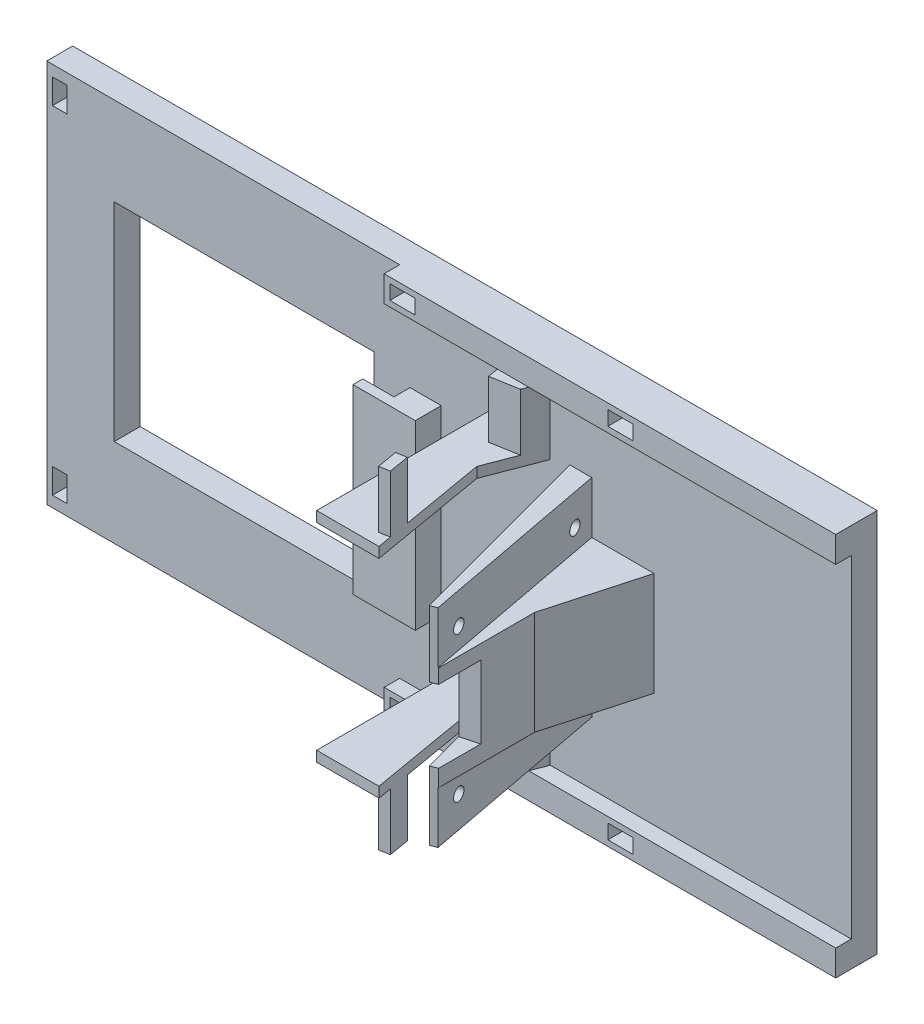
SolidWorks part; units mm, degrees
other "Marca1"
sketch "Croquis45" plane through (-59, -35, 38.8) normal (-0.8813, -0.0586, 0.4689) x (0.3892, -0.6526, 0.6501)
sketch "Croquis46" plane through (-59, -35, 38.8) normal (-0.8813, -0.0586, 0.4689) x (0.3892, -0.6526, 0.6501)
ref_plane "Alzado" through (0, 0, 0) normal (0, 0, 1) x (1, 0, 0)
ref_plane "Planta" through (0, 0, 0) normal (0, 1, 0) x (1, 0, 0)
ref_plane "Vista lateral" through (0, 0, 0) normal (1, 0, 0) x (0, 0, -1)
sketch "Croquis1" plane through (0, 0, 0) normal (0, 0, 1) x (1, 0, 0)
  line L1 (-59, -37) -> (59, -37)
  line L2 (-59, -37) -> (-59, 37)
  line L3 (-59, 37) -> (59, 37)
  line L4 (59, -37) -> (59, 37)
  line L5 (-59, -37) -> (59, 37) construction
  line L6 (-59, 37) -> (59, -37) construction
  point P0 (0, 0)
extrude "Saliente-Extruir1" add sketch "Croquis1" along normal blind 5
sketch "Croquis2" plane through (0, 0, 5) normal (0, 0, 1) x (1, 0, 0)
  line L4 (-46, 20) -> (4, 20)
  line L5 (4, 20) -> (4, -20)
  line L6 (4, -20) -> (-46, -20)
  line L7 (-46, -20) -> (-46, 20)
extrude "Cortar-Extruir1" cut sketch "Croquis2" against normal blind 5
sketch "Croquis3" plane through (0, 0, 5) normal (0, 0, 1) x (1, 0, 0)
  line L0 (59, 37) -> (59, 32)
  line L1 (59, -37) -> (59, 37) construction
  line L2 (59, 32) -> (9, 32)
  line L3 (9, 32) -> (9, 37)
  line L4 (59, 37) -> (-59, 37) construction
  line L5 (9, 37) -> (59, 37)
  line L6 (59, -37) -> (59, -32)
  line L7 (59, -32) -> (9, -32)
  line L8 (9, -32) -> (9, -37)
  line L9 (-59, -37) -> (59, -37) construction
  line L10 (9, -37) -> (59, -37)
extrude "Saliente-Extruir2" add sketch "Croquis3" along normal blind 3
sketch "Croquis4" plane through (0, 0, 8) normal (0, 0, 1) x (1, 0, 0)
  line L0 (59, 37) -> (9, 37) construction
  line L5 (56.9, 35.9) -> (52.1, 35.9)
  line L6 (56.9, 35.9) -> (56.9, 33.1)
  line L7 (56.9, 33.1) -> (52.1, 33.1)
  line L8 (52.1, 35.9) -> (52.1, 33.1)
  line L9 (10.1, 35.9) -> (14.9, 35.9)
  line L10 (10.1, 35.9) -> (10.1, 33.1)
  line L11 (10.1, 33.1) -> (14.9, 33.1)
  line L12 (14.9, 35.9) -> (14.9, 33.1)
  line L13 (10.1, -33.1) -> (14.9, -33.1)
  line L14 (10.1, -33.1) -> (10.1, -35.9)
  line L15 (10.1, -35.9) -> (14.9, -35.9)
  line L16 (14.9, -33.1) -> (14.9, -35.9)
  line L17 (56.9, -33.1) -> (52.1, -33.1)
  line L18 (56.9, -33.1) -> (56.9, -35.9)
  line L19 (56.9, -35.9) -> (52.1, -35.9)
  line L20 (52.1, -33.1) -> (52.1, -35.9)
  line L21 (-57.9, -34.9) -> (-55.1, -34.9)
  line L22 (-57.9, -34.9) -> (-57.9, -30.1)
  line L23 (-57.9, -30.1) -> (-55.1, -30.1)
  line L24 (-55.1, -34.9) -> (-55.1, -30.1)
  line L25 (-57.9, 34.9) -> (-55.1, 34.9)
  line L26 (-57.9, 34.9) -> (-57.9, 30.1)
  line L27 (-57.9, 30.1) -> (-55.1, 30.1)
  line L28 (-55.1, 34.9) -> (-55.1, 30.1)
  line L29 (9, 37) -> (9, 32) construction
  line L30 (9, -37) -> (59, -37) construction
  line L31 (-59, 37) -> (-59, -37) construction
  line L32 (9, 37) -> (-59, 37) construction
  line L33 (-59, -37) -> (9, -37) construction
  line L34 (59, -37) -> (59, -32) construction
  line L35 (59, 32) -> (59, 37) construction
  dimension "D1" = 1.1
  dimension "D2" = 1.1
  dimension "D3" = 1.1
  dimension "D4" = 1.1
  dimension "D5" = 1.1
  dimension "D6" = 2.1
  dimension "D7" = 1.1
  dimension "D8" = 2.1
  dimension "D9" = 1.1
  dimension "D10" = 2.1
  dimension "D11" = 2.1
extrude "Cortar-Extruir2" cut sketch "Croquis4" against normal blind 6
sketch "Croquis5" plane through (0, 0, 5) normal (0, 0, 1) x (1, 0, 0)
  line L0 (41, -20) -> (41, 20)
  line L1 (41, 20) -> (38, 20)
  line L2 (38, 20) -> (38, -20)
  line L3 (38, -20) -> (41, -20)
  line L4 (38, 0) -> (4, 0) construction
  line L5 (4, -20) -> (4, 20) construction
  point P0 (41, -20)
extrude "Cortar-Extruir3" cut sketch "Croquis5" against normal blind 3
sketch "Croquis6" plane through (0, 0, 2) normal (0, 0, 1) x (1, 0, 0)
  line L0 (41, 20) -> (41, -20)
  line L1 (41, -20) -> (53, -20)
  line L2 (38, -20) -> (41, -20) construction
  line L3 (53, -20) -> (53, 20)
  line L4 (41, 20) -> (38, 20) construction
  line L5 (53, 20) -> (41, 20)
extrude "Saliente-Extruir3" add sketch "Croquis6" along normal blind 40
sketch "Croquis7" plane through (0, -20, 0) normal (0, -1, 0) x (1, 0, 0)
  line L0 (41, 42) -> (51.718, 42) construction
  line L1 (53, 42) -> (41, 42) construction
  line L2 (51.718, 42) -> (41, 2)
  line L3 (41, 2) -> (41, 42)
  line L4 (41, 42) -> (51.718, 42)
  line L5 (38, 2) -> (41, 2) construction
  line L6 (41, 2) -> (41, 5) construction
  line L7 (53, 42) -> (41, 42) construction
  dimension "D1" = 15
sketch "Croquis8" plane through (0, 0, 5) normal (0, 0, 1) x (1, 0, 0)
  line L1 (17, 17.5) -> (17, -17.5)
  line L2 (17, -17.5) -> (13, -17.5)
  line L3 (13, -17.5) -> (13, 17.5)
  line L4 (13, 17.5) -> (17, 17.5)
extrude "Saliente-Extruir5" add sketch "Croquis8" along normal blind 5
sketch "Croquis10" plane through (13, 0, 0) normal (-1, 0, 0) x (0, 0, 1)
  line L0 (10, 17.5) -> (10, -17.5)
  line L6 (10, 17.5) -> (8.1, 17.5)
  line L7 (8.1, 17.5) -> (8.1, -17.5)
  line L8 (8.1, -17.5) -> (10, -17.5)
sketch "Croquis12" plane through (0, 0, 5) normal (0, 0, 1) x (1, 0, 0)
  line L0 (26, -19) -> (38, -19)
  line L2 (38, -19) -> (38, -32)
  line L3 (38, -32) -> (31, -32)
  line L5 (31, 32) -> (38, 32)
  line L8 (38, 32) -> (38, 19)
  line L9 (26, -19) -> (26, -21)
  line L10 (26, -21) -> (31, -21)
  line L11 (26, 19) -> (38, 19)
  line L12 (26, 19) -> (26, 21)
  line L13 (26, 21) -> (31, 21)
  line L14 (31, 32) -> (31, 21)
  line L15 (31, -21) -> (31, -32)
extrude "Saliente-Extruir7" add sketch "Croquis12" along normal blind 33
sketch "Croquis14" plane through (0, 32, 0) normal (0, 1, 0) x (1, 0, 0)
  line L0 (31, -38) -> (36, -38)
  line L1 (31, -38) -> (38, -38) construction
  line L2 (36, -38) -> (31, -9)
  line L3 (31, -38) -> (31, -5) construction
  line L4 (31, -9) -> (31, -38)
extrude "Cortar-Extruir6" cut sketch "Croquis14" against normal blind 11
sketch "Croquis16" plane through (0, 19, 0) normal (0, -1, 0) x (1, 0, 0)
  line L0 (38, 38) -> (38, 5)
  line L1 (38, 5) -> (33, 5)
  line L2 (33, 5) -> (33, 9)
  line L4 (38, 38) -> (33, 9)
extrude "Cortar-Extruir7" cut sketch "Croquis16" against normal blind 13
sketch "Croquis17" plane through (0, -32, 0) normal (0, -1, 0) x (1, 0, 0)
  line L0 (38, 38) -> (38, 5)
  line L1 (38, 5) -> (33, 5)
  line L2 (33, 5) -> (33, 9)
  line L3 (38, 38) -> (33, 9)
extrude "Cortar-Extruir8" cut sketch "Croquis17" against normal blind 13
sketch "Croquis18" plane through (0, -32, 0) normal (0, -1, 0) x (1, 0, 0)
  line L0 (31, 38) -> (36, 38)
  line L1 (36, 38) -> (31, 9)
  line L2 (31, 38) -> (31, 8) construction
  line L3 (31, 9) -> (31, 38)
extrude "Cortar-Extruir9" cut sketch "Croquis18" against normal blind 11
extrude "Saliente-Extruir9" add sketch "Croquis10" along normal blind 8
sketch "Croquis22" plane through (13, 0, 0) normal (-1, 0, 0) x (0, 0, 1)
  line L0 (8.1, -17.5) -> (5, -17.5)
  line L1 (5, -17.5) -> (5, 17.5)
  line L2 (5, 17.5) -> (8.1, 17.5)
  line L3 (8.1, 17.5) -> (5, 17.5) construction
  line L4 (8.1, 17.5) -> (8.1, -17.5)
extrude "Saliente-Extruir10" add sketch "Croquis22" along normal blind 2
extrude "Cortar-Extruir11" cut sketch "Croquis7" against normal blind 40
sketch "Croquis23" plane through (38, 0, 0) normal (1, 0, 0) x (0, 0, -1)
  line L0 (-2, 20) -> (-5, 20)
  line L1 (-5, 20) -> (-5, -20)
  line L2 (-5, -20) -> (-2, -20)
  line L3 (-2, -20) -> (-2, 20)
extrude "Saliente-Extruir11" add sketch "Croquis23" along normal blind 10
sketch "Croquis25" plane through (0, -20, 0) normal (0, -1, 0) x (1, 0, 0)
  line L0 (53, 42) -> (53, 5)
  line L1 (53, 5) -> (46, 5)
  line L3 (46, 5) -> (53, 42)
  line L4 (51.718, 42) -> (53, 42) construction
  line L7 (51.718, 42) -> (53, 42) construction
extrude "Cortar-Extruir12" cut sketch "Croquis25" against normal blind 10
sketch "Croquis26" plane through (0, 20, 0) normal (0, 1, 0) x (1, 0, 0)
  line L0 (53, -5) -> (53, -42)
  line L1 (53, -42) -> (46, -5)
  line L3 (46, -5) -> (53, -5)
  line L4 (51.718, -42) -> (53, -42) construction
extrude "Cortar-Extruir13" cut sketch "Croquis26" against normal blind 10
sketch "Croquis27" plane through (0, -20, 0) normal (0, -1, 0) x (1, 0, 0)
  line L0 (51.718, 42) -> (53, 42)
  line L1 (53, 42) -> (53, 41.4949)
  line L3 (53, 41.4949) -> (51.718, 42)
  line L4 (53, 5) -> (53, 42) construction
extrude "Cortar-Extruir14" cut sketch "Croquis27" against normal blind 40
sketch "Croquis28" plane through (37.7535, 0, -10.116) normal (-0.9659, 0, 0.2588) x (0.2588, 0, 0.9659)
  line L0 (20.8019, -14) -> (48.8019, -14) construction
  line L1 (48.8019, -14) -> (48.8019, 14) construction
  line L2 (48.8019, 14) -> (20.8019, 14) construction
  line L3 (20.8019, 14) -> (20.8019, -14) construction
  line L4 (20.8019, 14) -> (48.8019, -14) construction
  line L5 (48.8019, 14) -> (20.8019, -14) construction
  line L6 (34.8019, 0) -> (44.3019, 0) construction
  line L7 (44.3019, 0) -> (44.3019, 12.5) construction
  line L8 (44.3019, 12.5) -> (26.3019, 12.5) construction
  line L9 (26.3019, 12.5) -> (26.3019, -12.5) construction
  line L10 (26.3019, -12.5) -> (44.3019, -12.5) construction
  line L11 (44.3019, -12.5) -> (44.3019, 0) construction
  line L12 (34.8019, 20) -> (34.8019, -20) construction
  line L14 (15.6493, 20) -> (53.9545, 20) construction
  line L15 (15.6493, -20) -> (53.9545, -20) construction
  line L16 (53.9545, 0) -> (15.6493, 0) construction
  line L17 (53.9545, 20) -> (53.9545, -20) construction
  line L18 (15.6493, -20) -> (15.6493, 20) construction
  circle A0 centre (20.8019, 14) radius 1.25
  circle A1 centre (48.8019, 14) radius 1.25
  circle A2 centre (48.8019, -14) radius 1.25
  circle A3 centre (20.8019, -14) radius 1.25
  point P8 (34.8019, 0)
  point P28 (34.8019, 0)
extrude "Cortar-Extruir15" cut sketch "Croquis28" against normal blind 5
sketch "Croquis29" plane through (59, 0, 0) normal (1, 0, 0) x (0, 0, -1)
  line L2 (-8, 37) -> (0, 37)
  line L3 (0, 37) -> (0, -37)
  line L4 (0, -37) -> (-8, -37)
  line L5 (-8, -37) -> (-8, -32)
  line L6 (-8, -32) -> (-5, -32)
  line L7 (-5, -32) -> (-5, 32)
  line L8 (-8, 37) -> (-8, 32)
  line L9 (-8, 32) -> (-5, 32)
extrude "Saliente-Extruir12" add sketch "Croquis29" along normal blind 37
ref_plane "Plano1" through (28.5982, 0, -4.9307) normal (-0.9855, 0, 0.1699) x (0.1699, 0, 0.9855)
sketch "Croquis30" plane through (28.5982, 0, -4.9307) normal (-0.9855, 0, 0.1699) x (0.1699, 0, 0.9855)
  line L1 (14.1363, 32) -> (43.5641, 32)
  line L2 (14.1363, 32) -> (14.1363, 21)
  line L3 (14.1363, 21) -> (43.5641, 21)
  line L4 (43.5641, 32) -> (43.5641, 21)
extrude "Saliente-Extruir13" add sketch "Croquis30" against normal up to surface (1.9709 mm away) up to face at (35.5, 25.5, 23.5)
sketch "Croquis31" plane through (28.5982, 0, -4.9307) normal (-0.9855, 0, 0.1699) x (0.1699, 0, 0.9855)
  line L0 (23.1363, 26.5) -> (32.1363, 26.5) construction
  line L1 (14.1363, 21) -> (14.1363, 32) construction
  line L3 (14.1363, 26.5) -> (23.1363, 26.5) construction
  line L4 (32.1363, 26.5) -> (41.1363, 26.5) construction
  line L5 (14.1363, 31) -> (14.1363, 22) construction
  line L6 (14.1363, 31) -> (43.5641, 31) construction
  line L7 (43.5641, 21) -> (43.5641, 32) construction
  line L8 (14.1363, 22) -> (43.5641, 22) construction
  line L9 (23.1363, 31) -> (23.1363, 22) construction
  line L10 (14.1363, 31) -> (16.1363, 31)
  line L11 (14.1363, 31) -> (14.1363, 22)
  line L12 (14.1363, 22) -> (16.1363, 22)
  line L13 (16.1363, 31) -> (16.1363, 22)
  line L14 (32.1363, 31) -> (32.1363, 22) construction
  line L16 (23.1363, 31) -> (25.1363, 31)
  line L17 (23.1363, 31) -> (23.1363, 22)
  line L18 (23.1363, 22) -> (25.1363, 22)
  line L19 (25.1363, 31) -> (25.1363, 22)
  line L20 (32.1363, 31) -> (34.1363, 31)
  line L21 (32.1363, 31) -> (32.1363, 22)
  line L22 (32.1363, 22) -> (34.1363, 22)
  line L23 (34.1363, 31) -> (34.1363, 22)
  point P10 (14.1363, 26.5)
  point P18 (23.1363, 26.5)
  point P21 (32.1363, 26.5)
  dimension "D1" = 9
  dimension "D2" = 9
  dimension "D3" = 9
  dimension "D4" = 9
  dimension "D5" = 2
  dimension "D6" = 2
  dimension "D7" = 2
extrude "Saliente-Extruir14" [suppressed] add sketch "Croquis31" along normal blind 3
sketch "Croquis34" [suppressed] plane through (3.0034, 0, 16.2186) normal (0.1821, 0, 0.9833) x (0.9833, 0, -0.1821)
  line L0 (28.8429, 25.5) -> (25.8429, 25.5) construction
  line L1 (28.8429, 21) -> (28.8429, 30) construction
  line L2 (25.8429, 21) -> (25.8429, 30) construction
  line L3 (25.8429, 29) -> (25.8429, 22) construction
  line L5 (25.8429, 29) -> (28.8429, 29)
  line L6 (25.8429, 29) -> (25.8429, 22)
  line L7 (25.8429, 22) -> (28.8429, 22)
  line L8 (28.8429, 29) -> (28.8429, 22)
  point P9 (25.8429, 25.5)
  dimension "D1" = 7
extrude "Cortar-Extruir16" [suppressed] cut sketch "Croquis34" against normal blind 1
sketch "Croquis35" [suppressed] plane through (4.6422, 0, 25.0681) normal (0.1821, 0, 0.9833) x (0.9833, 0, -0.1821)
  line L0 (28.8429, 25.5) -> (25.8429, 25.5) construction
  line L1 (28.8429, 21) -> (28.8429, 30) construction
  line L2 (25.8429, 21) -> (25.8429, 30) construction
  line L3 (25.8429, 29) -> (25.8429, 22) construction
  line L5 (25.8429, 29) -> (28.8429, 29)
  line L6 (25.8429, 29) -> (25.8429, 22)
  line L7 (25.8429, 22) -> (28.8429, 22)
  line L8 (28.8429, 29) -> (28.8429, 22)
  point P9 (25.8429, 25.5)
  dimension "D1" = 7
extrude "Cortar-Extruir17" [suppressed] cut sketch "Croquis35" against normal blind 1
sketch "Croquis36" [suppressed] plane through (6.281, 0, 33.9176) normal (0.1821, 0, 0.9833) x (0.9833, 0, -0.1821)
  line L0 (28.8429, 25.5) -> (25.8429, 25.5) construction
  line L1 (28.8429, 21) -> (28.8429, 30) construction
  line L2 (25.8429, 21) -> (25.8429, 30) construction
  line L3 (25.8429, 29) -> (25.8429, 22) construction
  line L5 (25.8429, 29) -> (28.8429, 29)
  line L6 (25.8429, 29) -> (25.8429, 22)
  line L7 (25.8429, 22) -> (28.8429, 22)
  line L8 (28.8429, 29) -> (28.8429, 22)
  point P9 (25.8429, 25.5)
  dimension "D1" = 7
extrude "Cortar-Extruir18" [suppressed] cut sketch "Croquis36" against normal blind 1
sketch "Croquis37" [suppressed] plane through (28.3607, 0, -5.252) normal (-0.9833, 0, 0.1821) x (0.1821, 0, 0.9833)
  line L5 (23.4943, 29) -> (23.4943, 22) construction
  line L14 (23.4943, 30) -> (23.4943, 21) construction
  line L15 (32.4943, 29) -> (32.4943, 22) construction
  line L16 (32.4943, 30) -> (32.4943, 21) construction
  line L17 (41.9534, 29) -> (41.9534, 22) construction
  line L18 (41.9534, 21) -> (41.9534, 30) construction
  line L19 (15.4943, 25.5) -> (23.4943, 25.5) construction
  line L20 (15.4943, 22) -> (15.4943, 29) construction
  line L21 (23.4943, 25.5) -> (32.4943, 25.5) construction
  line L22 (32.4943, 25.5) -> (41.9534, 25.5) construction
  line L23 (23.4943, 29) -> (32.4943, 29) construction
  line L24 (32.4943, 29) -> (41.9534, 29) construction
  line L25 (23.4943, 22) -> (32.4943, 22) construction
  line L26 (32.4943, 22) -> (42.2674, 22) construction
  line L28 (23.4943, 29) -> (21.4943, 29)
  line L29 (23.4943, 29) -> (23.4943, 22)
  line L30 (23.4943, 22) -> (21.4943, 22)
  line L31 (21.4943, 29) -> (21.4943, 22)
  line L32 (32.4943, 29) -> (30.4943, 29)
  line L33 (32.4943, 29) -> (32.4943, 22)
  line L34 (32.4943, 22) -> (30.4943, 22)
  line L35 (30.4943, 29) -> (30.4943, 22)
  line L36 (41.9534, 29) -> (39.9534, 29)
  line L37 (41.9534, 29) -> (41.9534, 22)
  line L38 (41.9534, 22) -> (39.9534, 22)
  line L39 (39.9534, 29) -> (39.9534, 22)
  point P6 (23.4943, 25.5)
  point P12 (32.4943, 25.5)
  point P18 (41.9534, 25.5)
  dimension "D1" = 7
  dimension "D2" = 2
  dimension "D3" = 2
  dimension "D4" = 2
extrude "Cortar-Extruir19" [suppressed] cut sketch "Croquis37" against normal up to next
sketch "Croquis38" [suppressed] plane through (7.6393, 0, 41.252) normal (-0.1821, 0, -0.9833) x (-0.9833, 0, 0.1821)
  line L1 (-30.8095, 22) -> (-28.8429, 22)
  line L2 (-30.8095, 22) -> (-30.8095, 29)
  line L3 (-30.8095, 29) -> (-28.8429, 29)
  line L4 (-28.8429, 22) -> (-28.8429, 29)
extrude "Cortar-Extruir20" [suppressed] cut sketch "Croquis38" against normal up to next
sketch "Croquis39" [suppressed] plane through (2.8213, 0, 15.2353) normal (0.1821, 0, 0.9833) x (0.9833, 0, -0.1821)
  line L0 (25.8429, 22) -> (28.8429, 22) construction
  line L1 (25.8429, 29) -> (26.8429, 29)
  line L2 (25.8429, 29) -> (25.8429, 22)
  line L3 (25.8429, 22) -> (26.8429, 22)
  line L4 (26.8429, 29) -> (26.8429, 22)
  dimension "D1" = 1
extrude "Saliente-Extruir15" [suppressed] add sketch "Croquis39" along normal up to surface (1 mm away)
sketch "Croquis40" [suppressed] plane through (4.4601, 0, 24.0848) normal (0.1821, 0, 0.9833) x (0.9833, 0, -0.1821)
  line L0 (25.8429, 22) -> (28.8429, 22) construction
  line L1 (25.8429, 29) -> (26.8429, 29)
  line L2 (25.8429, 29) -> (25.8429, 22)
  line L3 (25.8429, 22) -> (26.8429, 22)
  line L4 (26.8429, 29) -> (26.8429, 22)
  dimension "D1" = 1
extrude "Saliente-Extruir16" [suppressed] add sketch "Croquis40" along normal blind 1
sketch "Croquis41" [suppressed] plane through (6.099, 0, 32.9343) normal (0.1821, 0, 0.9833) x (0.9833, 0, -0.1821)
  line L1 (25.8429, 29) -> (26.8429, 29)
  line L2 (25.8429, 29) -> (25.8429, 22)
  line L3 (25.8429, 22) -> (26.8429, 22)
  line L4 (26.8429, 29) -> (26.8429, 22)
  dimension "D1" = 1
extrude "Saliente-Extruir17" [suppressed] add sketch "Croquis41" along normal blind 1
mirror "Simetría3" about plane through (0, 0, 0) normal (0, 1, 0) of "Saliente-Extruir14", "Cortar-Extruir16", "Cortar-Extruir17", "Cortar-Extruir18", "Cortar-Extruir19", "Cortar-Extruir20", "Saliente-Extruir15", "Saliente-Extruir16", "Saliente-Extruir17", "Saliente-Extruir13"
chamfer "Chaflán1" distance 5 distance2 18 1 edges at (53, 0, 5) tangent propagation no first distance on face at (46.701, 0, 5)
chamfer "Chaflán2" distance 13 distance2 5 1 edges at (33, 25.5, 5) first distance on face at (33, 26.8, 7.2)
chamfer "Chaflán3" distance 13 distance2 5 1 edges at (33, -25.5, 5) first distance on face at (33, -26.8, 7.2)
sketch "Croquis42" [suppressed] plane through (0, 0, 36) normal (0, 0, 1) x (1, 0, 0)
  line L0 (26, 21) -> (26, 19)
  line L1 (26, 19) -> (38, 19)
  line L2 (38, 19) -> (38, 22)
  line L3 (38, 22) -> (36, 22)
  line L4 (36, 22) -> (36, 21)
  line L5 (36, 21) -> (26, 21)
  line L6 (38, 30) -> (38, 29)
  line L7 (38, 29) -> (36, 29)
  line L8 (36, 29) -> (36, 30)
  line L9 (36, 30) -> (38, 30)
extrude "Saliente-Extruir18" [suppressed] add sketch "Croquis42" along normal blind 2.8
mirror "Simetría5" [suppressed] about plane through (0, 0, 0) normal (0, 1, 0)
sketch "Croquis43" [suppressed] plane through (0, 29, 0) normal (0, -1, 0) x (1, 0, 0)
  line L1 (38, 36) -> (36, 36)
  line L2 (38, 36) -> (38, 38.8)
  line L3 (38, 38.8) -> (36, 38.8)
  line L4 (36, 36) -> (36, 38.8)
extrude "Saliente-Extruir19" [suppressed] add sketch "Croquis43" along normal up to next
mirror "Simetría6" [suppressed] about plane through (0, 0, 0) normal (0, 1, 0)
sketch "Croquis51" plane through (37.7535, 0, -10.116) normal (-0.9659, 0, 0.2588) x (0.2588, 0, 0.9659)
  line L0 (53.9545, -6.7669) -> (53.9545, 7.2331)
  line L1 (53.9545, 20) -> (53.9545, -20) construction
  line L2 (53.9545, 7.2331) -> (45.9545, 7.2331)
  line L3 (45.9545, 7.2331) -> (45.9545, -6.7669)
  line L4 (45.9545, -6.7669) -> (53.9545, -6.7669)
  point P5 (53.9545, 0.2331)
extrude "Cortar-Extruir23" cut sketch "Croquis51" against normal blind 10
sketch "Croquis52" plane through (28.5982, 0, -4.9307) normal (-0.9855, 0, 0.1699) x (0.1699, 0, 0.9855)
  line L0 (24.1944, -32) -> (10.0744, -32) construction
  line L2 (24.1944, -32) -> (24.1944, -21)
  line L3 (14.1363, -21) -> (43.5641, -21) construction
  line L5 (15.1944, -32) -> (15.1944, -21)
  line L6 (15.1944, -21) -> (24.1944, -21)
  line L7 (24.1944, -32) -> (15.1944, -32)
  line L9 (29.1944, -32) -> (29.1944, -21)
  line L19 (37.1944, -32) -> (37.1944, -21)
  line L20 (37.1944, -21) -> (29.1944, -21)
  line L21 (29.1944, -32) -> (37.1944, -32)
  line L23 (14.1363, -32) -> (43.5641, -32) construction
  line L24 (41.1944, -32) -> (41.1944, -21)
  line L25 (41.1944, -21) -> (45.7342, -21)
  line L26 (45.7342, -21) -> (45.7342, -32)
  line L27 (45.7342, -32) -> (41.1944, -32)
  dimension "D1" = 5
extrude "Cortar-Extruir25" cut sketch "Croquis52" against normal blind 10
sketch "Croquis53" plane through (0, -32, 0) normal (0, -1, 0) x (1, 0, 0)
  line L0 (31.1798, 10.0428) -> (30.1225, 3.9106) construction
  line L1 (31, 9) -> (30.1225, 3.9106)
  line L2 (30.1225, 3.9106) -> (31.1798, 3.9106)
  line L3 (31.1798, 3.9106) -> (31, 9)
extrude "Saliente-Extruir20" add sketch "Croquis53" against normal blind 12
mirror "Simetría8" about plane through (0, 0, 0) normal (0, 1, 0) of "Saliente-Extruir20", "Cortar-Extruir25"
sketch "Croquis54" plane through (28.5982, 0, -4.9307) normal (-0.9855, 0, 0.1699) x (0.1699, 0, 0.9855)
  line L0 (24.1944, 32) -> (29.1944, 32)
  line L1 (29.1944, 32) -> (29.1944, 21)
  line L2 (29.1944, 21) -> (24.1944, 21)
  line L3 (24.1944, 21) -> (24.1944, 32)
extrude "Cortar-Extruir26" cut sketch "Croquis54" against normal blind 10
sketch "Croquis55" plane through (28.5982, 0, -4.9307) normal (-0.9855, 0, 0.1699) x (0.1699, 0, 0.9855)
  line L4 (24.1944, -32) -> (29.1944, -32)
  line L5 (29.1944, -32) -> (29.1944, -21)
  line L6 (29.1944, -21) -> (24.1944, -21)
  line L7 (24.1944, -21) -> (24.1944, -32)
extrude "Cortar-Extruir30" cut sketch "Croquis55" against normal blind 10
